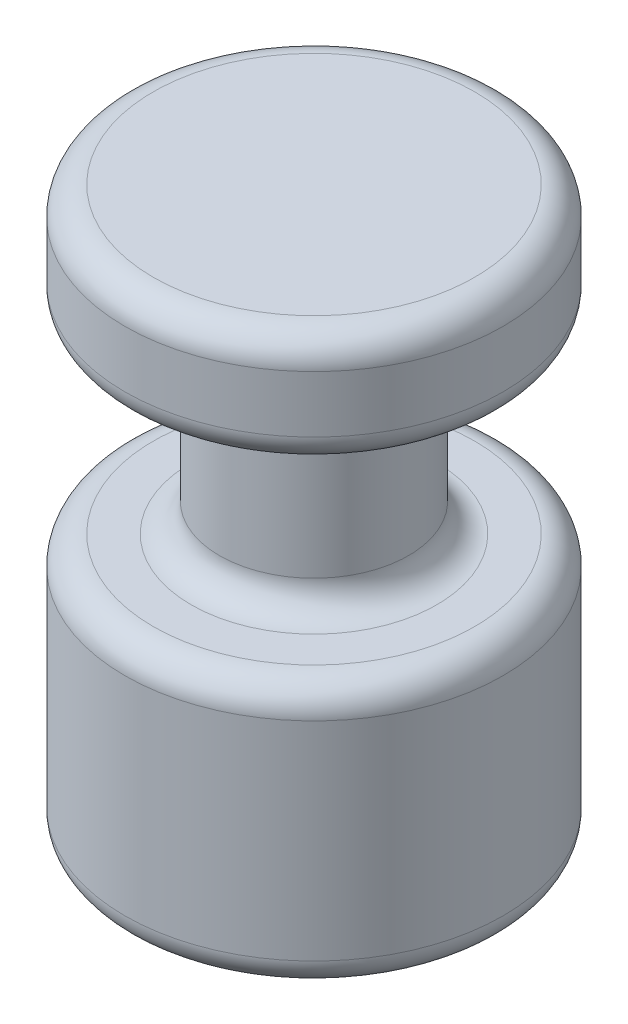
SolidWorks part; units mm, degrees
ref_plane "Front Plane" through (0, 0, 0) normal (0, 0, 1) x (1, 0, 0)
ref_plane "Top Plane" through (0, 0, 0) normal (0, 1, 0) x (1, 0, 0)
ref_plane "Right Plane" through (0, 0, 0) normal (1, 0, 0) x (0, 0, -1)
sketch "Sketch1" plane through (0, 0, 0) normal (0, 1, 0) x (1, 0, 0)
  line L1 (-2.5, 2.5) -> (2.5, 2.5)
  line L2 (-2.5, 2.5) -> (-2.5, -2.5)
  line L3 (-2.5, -2.5) -> (2.5, -2.5)
  line L4 (2.5, 2.5) -> (2.5, -2.5)
  line L5 (-2.5, 2.5) -> (2.5, -2.5) construction
  line L6 (-2.5, -2.5) -> (2.5, 2.5) construction
  circle A1 centre (0, 0) radius 5
  point P7 (0, 0)
  dimension "D2" = 10
  dimension "D1" = 5
extrude "Boss-Extrude1" add sketch "Sketch1" along normal blind 5
sketch "Sketch2" plane through (0, 5, 0) normal (0, 1, 0) x (1, 0, 0)
  circle A0 centre (0, 0) radius 5
  dimension "D1" = 10
extrude "Boss-Extrude2" add sketch "Sketch2" along normal blind 2
sketch "Sketch3" plane through (0, 7, 0) normal (0, 1, 0) x (1, 0, 0)
  circle A0 centre (0, 0) radius 2.5
  dimension "D1" = 5
extrude "Boss-Extrude3" add sketch "Sketch3" along normal blind 5
sketch "Sketch4" plane through (0, 12, 0) normal (0, 1, 0) x (1, 0, 0)
  circle A0 centre (0, 0) radius 5
extrude "Boss-Extrude4" add sketch "Sketch4" along normal blind 3
fillet "Fillet7" radius 0.75 18 edges at (0, 15, 5) (0, 12, 5) (0, 12, 2.5) (0, 5, 2.5) (0, 0, 2.5) (2.5, 5, 0) (2.5, 2.5, 2.5) (2.5, 0, 0) (0, 5, -2.5) (2.5, 2.5, -2.5) (0, 0, -2.5) (-2.5, 2.5, 2.5) (-2.5, 5, 0) (-2.5, 2.5, -2.5) (-2.5, 0, 0) (0, 0, 5) (0, 7, 2.5) (0, 7, 5)
